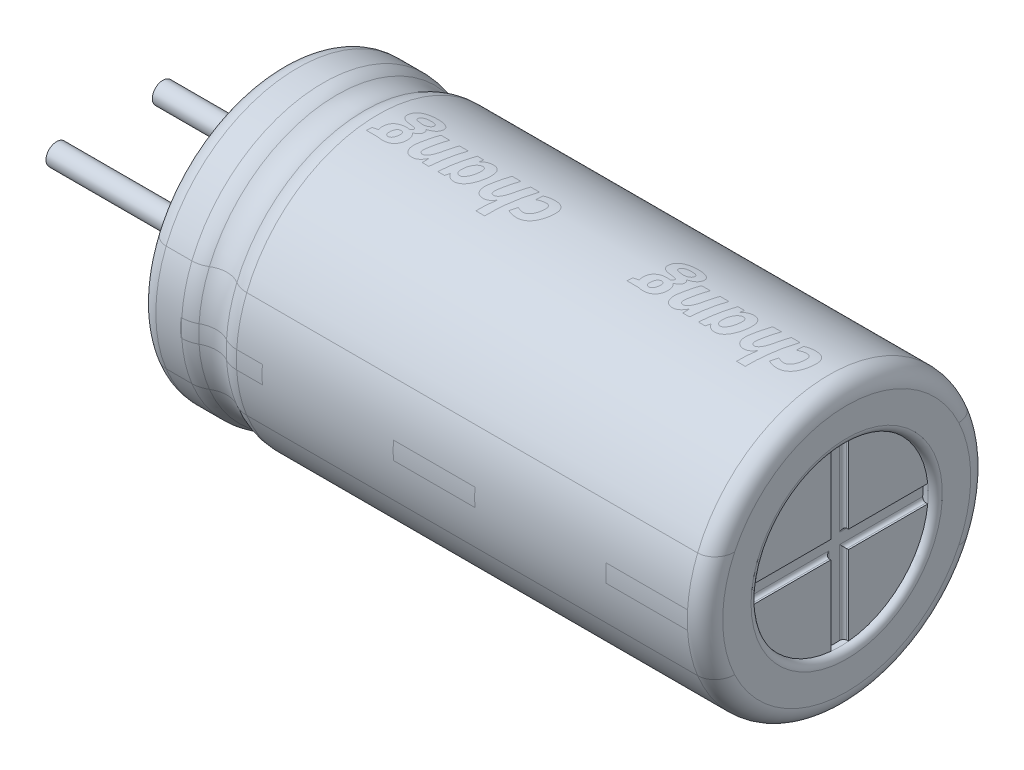
SolidWorks part; units mm, degrees
ref_plane "Front Plane" through (0, 0, 0) normal (0, 0, 1) x (1, 0, 0)
ref_plane "Top Plane" through (0, 0, 0) normal (0, 1, 0) x (1, 0, 0)
ref_plane "Right Plane" through (0, 0, 0) normal (1, 0, 0) x (0, 0, -1)
sketch "Эскиз1" plane through (0, 0, 0) normal (0, 0, 1) x (1, 0, 0)
  line L0 (-7.1191, 0) -> (15.7225, 0) construction
  line L1 (0, 0) -> (0, 4)
  line L2 (0, 4) -> (1.4708, 4)
  line L3 (16, 4) -> (16, 0)
  line L4 (16, 0) -> (0, 0)
  line L5 (2.5292, 4) -> (16, 4)
  arc A0 (1.4708, 4) -> (2.5292, 4) centre (2, 4.6) ccw
  dimension "D3" = 1.6
  dimension "D1" = 4
  dimension "D2" = 16
  dimension "D4" = 0.6
  dimension "D5" = 2
revolve "Повернуть1" add sketch "Эскиз1" angle 360 about L0
fillet "Скругление1" radius 0.8 2 edges at (2.5292, 0, 4) (1.4708, 0, 4)
sketch "Эскиз2" plane through (16, 0, 0) normal (1, 0, 0) x (0, 0, -1)
  circle A0 centre (0, 0) radius 2.5
  dimension "D1" = 5
extrude "Вырез-Вытянуть1" cut sketch "Эскиз2" against normal blind 0.2
fillet "Скругление2" radius 0.5 1 edges at (16, 0, 4)
sketch "Эскиз4" plane through (15.8, 0, 0) normal (1, 0, 0) x (0, 0, -1)
  line L0 (0, 4.2935) -> (0, -4.219) construction
  line L1 (-4.6234, 0) -> (4.6872, 0) construction
  line L2 (-0.25, 2.4875) -> (-0.25, 0.25)
  line L3 (-0.25, 0.25) -> (-2.4875, 0.25)
  line L4 (0.25, 0.25) -> (2.4875, 0.25)
  line L5 (0.25, 2.4875) -> (0.25, 0.25)
  line L6 (0.25, -0.25) -> (2.4875, -0.25)
  line L7 (-0.25, -0.25) -> (-2.4875, -0.25)
  line L8 (0.25, -2.4875) -> (0.25, -0.25)
  line L9 (-0.25, -2.4875) -> (-0.25, -0.25)
  circle A0 centre (0, 0) radius 2.5 construction
  arc A1 (-2.4875, 0.25) -> (-2.4875, -0.25) centre (0, 0) ccw
  arc A2 (0.25, 2.4875) -> (-0.25, 2.4875) centre (0, 0) ccw
  arc A3 (2.4875, -0.25) -> (2.4875, 0.25) centre (0, 0) ccw
  arc A4 (-0.25, -2.4875) -> (0.25, -2.4875) centre (0, 0) ccw
  dimension "D1" = 0.25
  dimension "D2" = 0.25
extrude "Вырез-Вытянуть2" cut sketch "Эскиз4" against normal blind 0.15
fillet "Скругление3" radius 0.1 8 edges at (15.65, 0.25, -1.3687) (15.65, 0.25, 1.3687) (15.65, -1.3687, -0.25) (15.65, -1.3687, 0.25) (15.65, 1.3687, 0.25) (15.65, -0.25, 1.3687) (15.65, -0.25, -1.3687) (15.65, 1.3687, -0.25)
sketch "Эскиз5" plane through (0, 0, 0) normal (-1, 0, 0) x (0, 0, 1)
  line L0 (-4.6447, 0) -> (4.4319, 0) construction
  line L1 (0, 5.1896) -> (0, -5.2514) construction
  circle A0 centre (0, 0) radius 2.5
  dimension "D1" = 5
extrude "Вырез-Вытянуть3" cut sketch "Эскиз5" against normal blind 0.2
sketch "Эскиз6" plane through (0.2, 0, 0) normal (-1, 0, 0) x (0, 0, 1)
  line L0 (-4.3787, 0) -> (4.666, 0) construction
  line L1 (0, 4.2084) -> (0, -4.368) construction
  circle A0 centre (-1.5, 0) radius 0.3
  circle A1 centre (1.5, 0) radius 0.3
  dimension "D1" = 0.6
  dimension "D2" = 1.5
extrude "Бобышка-Вытянуть2" add sketch "Эскиз6" along normal blind 5
fillet "Скругление4" radius 0.5 1 edges at (0, 0, 4)
ref_plane "Плоскость1" through (0, 0, 4.5) normal (0, 0, 1) x (1, 0, 0)
ref_plane "Плоскость2" through (0, 0, 4.2) normal (0, 0, 1) x (1, 0, 0)
sketch "Эскиз7" plane through (0, 0, 4.2) normal (0, 0, 1) x (1, 0, 0)
  line L0 (12.2056, 0) -> (-5.2275, 0) construction
  line L1 (16, -3.5) -> (16, 3.5) construction
  line L2 (-1.132, -1.5) -> (16.2714, -1.5)
  line L3 (-1.132, -1.5) -> (-1.132, 1.5)
  line L4 (-1.132, 1.5) -> (16.2714, 1.5)
  line L5 (16.2714, -1.5) -> (16.2714, 1.5)
  line L6 (-1.132, -1.5) -> (16.2714, 1.5) construction
  line L7 (-1.132, 1.5) -> (16.2714, -1.5) construction
  line L8 (15.5, -0.25) -> (13.2, -0.25)
  line L9 (15.5, -0.25) -> (15.5, 0.25)
  line L10 (15.5, 0.25) -> (13.2, 0.25)
  line L11 (13.2, -0.25) -> (13.2, 0.25)
  line L12 (15.5, -0.25) -> (13.2, 0.25) construction
  line L13 (15.5, 0.25) -> (13.2, -0.25) construction
  line L14 (9.5, -0.25) -> (9.5, 0.25)
  line L15 (9.5, -0.25) -> (7.2, -0.25)
  line L16 (7.2, -0.25) -> (7.2, 0.25)
  line L17 (9.5, 0.25) -> (7.2, 0.25)
  line L18 (3.5, -0.25) -> (3.5, 0.25)
  line L19 (3.5, -0.25) -> (1.2, -0.25)
  line L20 (1.2, -0.25) -> (1.2, 0.25)
  line L21 (3.5, 0.25) -> (1.2, 0.25)
  point P3 (7.5697, 0)
  point P8 (14.35, 0)
  dimension "D1" = 3
  dimension "D2" = 2.3
  dimension "D3" = 0.5
  dimension "D4" = 0.5
  dimension "D5" = 3
split line "Разделяющая линия1"
fillet "Скругление6" radius 0.2 1 edges at (0, 0, 2.5)
ref_plane "Плоскость3" through (0, 4.2, 0) normal (0, 1, 0) x (1, 0, 0)
sketch "Эскиз8" plane through (0, 4.2, 0) normal (0, 1, 0) x (1, 0, 0)
  line L0 (-0.5509, 0) -> (16.6512, 0) construction
  line L1 (16, 0.4) -> (0, 0.4) construction
  line L5 (16, -3.1623) -> (16, 3.1623) construction
  line L6 (0, 3.5) -> (0, -3.5) construction
  text T0 "  chang      chang" font "Open Sans" height 1.2
  dimension "D1" = 0.4
ref_plane "Плоскость4" through (0, -4.2, 0) normal (0, 1, 0) x (1, 0, 0)
sketch "Эскиз9" plane through (0, -4.2, 0) normal (0, 1, 0) x (1, 0, 0)
  line L0 (16.4383, 0) -> (-0.267, 0) construction
  line L1 (16, -0.4) -> (0, -0.4) construction
  line L5 (16, -3.1623) -> (16, 3.1623) construction
  line L6 (0, 3.5) -> (0, -3.5) construction
  text T0 "  -40+105ºC     -40+105ºC" font "Arial" height 0.8
  dimension "D1" = 0.4
split line "Разделяющая линия10"
split line "Разделяющая линия11"
fillet "Скругление5" radius 0.2 1 edges at (16, 0, -2.5)
